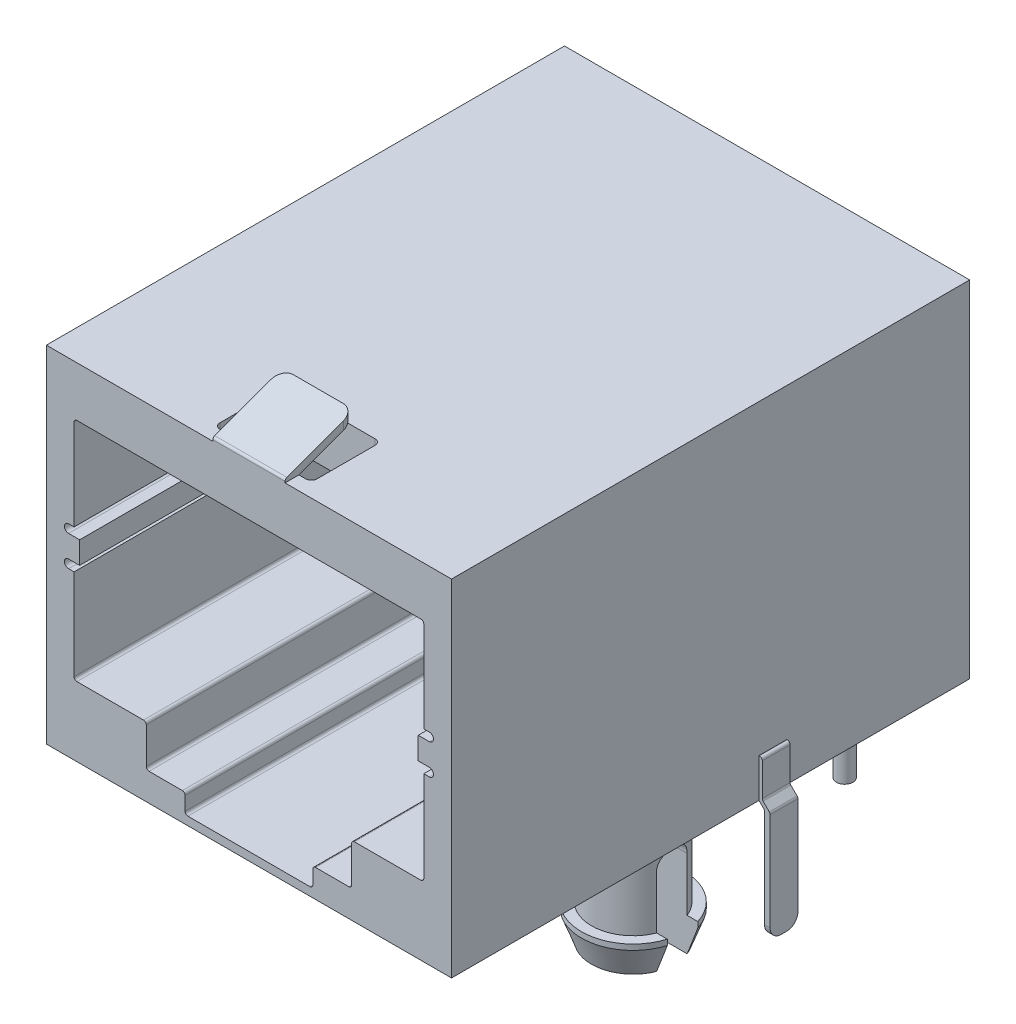
SolidWorks part; units mm, degrees
ref_plane "Plano frontal" through (0, 0, 0) normal (0, 0, 1) x (1, 0, 0)
ref_plane "Plano superior" through (0, 0, 0) normal (0, 1, 0) x (1, 0, 0)
ref_plane "Plano direito" through (0, 0, 0) normal (1, 0, 0) x (0, 0, -1)
sketch "Esboço1" plane through (0, 0, 0) normal (0, 0, 1) x (1, 0, 0)
  line L0 (0, 36.8425) -> (0, 0) construction
  line L2 (-7.3, 12.95) -> (7.3, 12.95)
  line L3 (-7.3, 12.95) -> (-7.3, 0.5)
  line L4 (-7.3, 0.5) -> (7.3, 0.5)
  line L5 (7.3, 12.95) -> (7.3, 0.5)
  line L6 (-7.3, 12.95) -> (7.3, 0.5) construction
  line L7 (-7.3, 0.5) -> (7.3, 12.95) construction
  point P3 (0, 6.725)
  dimension "D1" = 0.5
  dimension "D2" = 12.45
  dimension "D3" = 14.6
extrude "Ressalto-extrusão1" add sketch "Esboço1" along normal blind 9.335 and the other way blind 9.335
sketch "Esboço2" plane through (0, 0, 9.335) normal (0, 0, 1) x (1, 0, 0)
  line L0 (0, 12.95) -> (0, 0.5) construction
  line L1 (7.3, 12.95) -> (-7.3, 12.95) construction
  line L2 (-7.3, 0.5) -> (7.3, 0.5) construction
  line L3 (6.2, 11.15) -> (-6.2, 11.15)
  line L4 (-6.3, 11.15) -> (-6.3, 3) construction
  line L5 (-6.3, 7.075) -> (-2.7204, 7.075) construction
  line L6 (-6.3, 11.05) -> (-6.3, 7.775)
  line L7 (-6.3, 7.775) -> (-6.5, 7.775)
  line L8 (-6.5, 7.775) -> (-6.5, 7.475) construction
  line L9 (-6.2, 3) -> (-3.8, 3)
  line L10 (-3.7, 2.9) -> (-3.7, 1.6)
  line L11 (-3.6, 1.5) -> (-2.4, 1.5)
  line L12 (-2.3, 1.4) -> (-2.3, 0.9)
  line L13 (-2.2, 0.8) -> (2.2, 0.8)
  line L14 (-6.5, 7.475) -> (-6.1, 7.475)
  line L15 (-6.1, 7.475) -> (-6.1, 6.675)
  line L16 (-7.3, 12.95) -> (-7.3, 0.5) construction
  line L17 (-6.3, 3.1) -> (-6.3, 6.375)
  line L18 (-6.5, 6.675) -> (-6.1, 6.675)
  line L19 (-6.3, 6.375) -> (-6.5, 6.375)
  line L20 (6.5, 7.775) -> (6.5, 7.475) construction
  line L21 (6.3, 7.075) -> (2.7204, 7.075) construction
  line L22 (6.3, 11.15) -> (6.3, 3) construction
  line L23 (6.3, 6.375) -> (6.5, 6.375)
  line L24 (6.5, 6.675) -> (6.1, 6.675)
  line L25 (6.3, 3.1) -> (6.3, 6.375)
  line L26 (6.1, 7.475) -> (6.1, 6.675)
  line L27 (6.5, 7.475) -> (6.1, 7.475)
  line L28 (2.3, 1.4) -> (2.3, 0.9)
  line L29 (3.6, 1.5) -> (2.4, 1.5)
  line L30 (3.7, 2.9) -> (3.7, 1.6)
  line L31 (6.2, 3) -> (3.8, 3)
  line L32 (6.3, 7.775) -> (6.5, 7.775)
  line L33 (6.3, 11.05) -> (6.3, 7.775)
  arc A0 (-6.5, 7.775) -> (-6.5, 7.475) centre (-6.5, 7.625) ccw
  arc A1 (-6.5, 6.375) -> (-6.5, 6.675) centre (-6.5, 6.525) cw
  arc A2 (-2.3, 0.9) -> (-2.2, 0.8) centre (-2.2, 0.9) ccw
  arc A3 (-2.4, 1.5) -> (-2.3, 1.4) centre (-2.4, 1.4) cw
  arc A4 (-3.7, 1.6) -> (-3.6, 1.5) centre (-3.6, 1.6) ccw
  arc A5 (-3.8, 3) -> (-3.7, 2.9) centre (-3.8, 2.9) cw
  arc A6 (-6.3, 3.1) -> (-6.2, 3) centre (-6.2, 3.1) ccw
  arc A7 (-6.2, 11.15) -> (-6.3, 11.05) centre (-6.2, 11.05) ccw
  arc A8 (6.2, 11.15) -> (6.3, 11.05) centre (6.2, 11.05) cw
  arc A9 (6.3, 3.1) -> (6.2, 3) centre (6.2, 3.1) cw
  arc A10 (3.8, 3) -> (3.7, 2.9) centre (3.8, 2.9) ccw
  arc A11 (3.7, 1.6) -> (3.6, 1.5) centre (3.6, 1.6) cw
  arc A12 (2.4, 1.5) -> (2.3, 1.4) centre (2.4, 1.4) ccw
  arc A13 (2.3, 0.9) -> (2.2, 0.8) centre (2.2, 0.9) cw
  arc A14 (6.5, 6.375) -> (6.5, 6.675) centre (6.5, 6.525) ccw
  arc A15 (6.5, 7.775) -> (6.5, 7.475) centre (6.5, 7.625) cw
  point P6 (3.7, 1.5)
  point P25 (-6.5, 6.525)
  point P30 (-6.1, 7.075)
  point P34 (-2.3, 1.5)
  point P37 (-3.7, 1.5)
  point P77 (0, 0.8)
  point P78 (0, 11.15)
  point P79 (2.3, 1.5)
  point P80 (6.1, 7.075)
  dimension "D11" = 0.1
  dimension "D1" = 0.3
  dimension "D2" = 0.4
  dimension "D3" = 1.8
  dimension "D4" = 1
  dimension "D5" = 0.2
  dimension "D6" = 0.2
  dimension "D7" = 2.5
  dimension "D8" = 2.6
  dimension "D9" = 1.4
  dimension "D10" = 1
  dimension "D12" = 0.3
extrude "Corte-extrusão1" cut sketch "Esboço2" against normal blind 13
sketch "Esboço3" plane through (0, 0.5, 0) normal (0, -1, 0) x (1, 0, 0)
  line L0 (0, 9.335) -> (0, -9.335) construction
  line L1 (-7.3, 9.335) -> (7.3, 9.335) construction
  line L2 (-7.3, -9.335) -> (7.3, -9.335) construction
  circle A0 centre (-5.715, 1.205) radius 1.5
  circle A1 centre (-4.445, -5.145) radius 0.3
  circle A2 centre (-3.175, -7.685) radius 0.3
  circle A3 centre (5.715, 1.205) radius 1.5
  circle A4 centre (-1.905, -5.145) radius 0.3
  circle A5 centre (-0.635, -7.685) radius 0.3
  circle A6 centre (0.635, -5.145) radius 0.3
  circle A7 centre (1.905, -7.685) radius 0.3
  circle A8 centre (3.175, -5.145) radius 0.3
  circle A9 centre (4.445, -7.685) radius 0.3
  dimension "D1" = 0.6
  dimension "D2" = 0.6
  dimension "D9" = 3
  dimension "D3" = 1.27
  dimension "D4" = 1.27
  dimension "D5" = 5.715
  dimension "D6" = 8.13
  dimension "D7" = 6.35
  dimension "D8" = 2.54
  dimension "D10" = 4
extrude "Ressalto-extrusão2" add sketch "Esboço3" along normal blind 3.68
sketch "Esboço4" plane through (0, -3.18, 0) normal (0, -1, 0) x (1, 0, 0)
  circle A0 centre (-5.715, 1.205) radius 1.5 construction
  circle A1 centre (5.715, 1.205) radius 1.5 construction
  circle A2 centre (-5.715, 1.205) radius 1.5
  circle A3 centre (5.715, 1.205) radius 1.5
extrude "Ressalto-extrusão3" add sketch "Esboço4" against normal blind 1 draft 20 draft outward yes
sketch "Esboço5" plane through (0, -2.18, 0) normal (0, 1, 0) x (1, 0, 0)
  circle A0 centre (-5.715, -1.205) radius 1.864 construction
  circle A1 centre (5.715, -1.205) radius 1.864 construction
  circle A2 centre (-5.715, -1.205) radius 1.864
  circle A3 centre (5.715, -1.205) radius 1.864
extrude "Ressalto-extrusão4" add sketch "Esboço5" along normal blind 0.2
sketch "Esboço7" plane through (0, 0.5, 0) normal (0, -1, 0) x (1, 0, 0)
  line L0 (0, 9.335) -> (0, -9.335) construction
  line L1 (-7.3, 9.335) -> (7.3, 9.335) construction
  line L2 (-7.3, -9.335) -> (7.3, -9.335) construction
  line L3 (-3.175, -7.985) -> (-3.175, 9.335) construction
  line L4 (-3.175, -7.985) -> (-3.175, -9.335) construction
  line L5 (-3.825, 7.1522) -> (-2.525, 7.1522)
  line L6 (-3.825, 7.1522) -> (-3.825, 2.6522)
  line L7 (-3.825, 2.6522) -> (-2.525, 2.6522)
  line L8 (-2.525, 7.1522) -> (-2.525, 2.6522)
  line L9 (-3.825, 7.1522) -> (-2.525, 2.6522) construction
  line L10 (-3.825, 2.6522) -> (-2.525, 7.1522) construction
  line L11 (-3.825, -8.2792) -> (-2.525, -8.2792)
  line L12 (-3.825, -8.2792) -> (-3.825, -9.1461)
  line L13 (-3.825, -9.1461) -> (-2.525, -9.1461)
  line L14 (-2.525, -8.2792) -> (-2.525, -9.1461)
  line L15 (-3.825, -8.2792) -> (-2.525, -9.1461) construction
  line L16 (-3.825, -9.1461) -> (-2.525, -8.2792) construction
  line L17 (3.825, -9.1461) -> (2.525, -8.2792) construction
  line L18 (3.825, -8.2792) -> (2.525, -9.1461) construction
  line L19 (3.825, 2.6522) -> (2.525, 7.1522) construction
  line L20 (3.825, 7.1522) -> (2.525, 2.6522) construction
  line L21 (3.175, -7.985) -> (3.175, -9.335) construction
  line L22 (3.175, -7.985) -> (3.175, 9.335) construction
  line L23 (2.525, -8.2792) -> (2.525, -9.1461)
  line L24 (3.825, -9.1461) -> (2.525, -9.1461)
  line L25 (3.825, -8.2792) -> (3.825, -9.1461)
  line L26 (3.825, -8.2792) -> (2.525, -8.2792)
  line L27 (2.525, 7.1522) -> (2.525, 2.6522)
  line L28 (3.825, 2.6522) -> (2.525, 2.6522)
  line L29 (3.825, 7.1522) -> (3.825, 2.6522)
  line L30 (3.825, 7.1522) -> (2.525, 7.1522)
  circle A0 centre (-3.175, -7.685) radius 0.3 construction
  circle A1 centre (-3.175, -7.685) radius 0.3 construction
  point P12 (-3.175, 4.9022)
  point P18 (-3.175, -8.7126)
  point P35 (3.175, -8.7126)
  point P36 (3.175, 4.9022)
  dimension "D1" = 2.1828
  dimension "D2" = 1.3
  dimension "D3" = 4.5
  dimension "D4" = 1.3
extrude "Ressalto-extrusão5" add sketch "Esboço7" along normal blind 0.5
sketch "Esboço8" plane through (7.3, 0, 0) normal (1, 0, 0) x (0, 0, -1)
  line L0 (-1.205, -3.18) -> (-1.205, 4.3732) construction
  line L1 (-2.705, -3.18) -> (0.295, -3.18) construction
  line L2 (-1.755, -0.05) -> (-1.755, -3.18)
  line L3 (-0.655, -0.05) -> (-0.655, -3.18)
  line L4 (9.335, 0.5) -> (-9.335, 0.5) construction
  line L5 (-1.755, -3.18) -> (-0.655, -3.18)
  arc A0 (-0.655, -0.05) -> (-1.755, -0.05) centre (-1.205, -0.05) ccw
  dimension "D1" = 1.1
extrude "Corte-extrusão2" cut sketch "Esboço8" against normal through all and the other way through all
ref_plane "Plano2" through (0, 0, -2.245) normal (0, 0, 1) x (1, 0, 0)
sketch "Esboço9" plane through (0, 0, -2.245) normal (0, 0, 1) x (1, 0, 0)
  line L0 (-7.3, 1.9) -> (-7.32, 1.9)
  line L1 (-7.3, 12.95) -> (-7.3, 0.5) construction
  line L2 (-7.42, 1.8) -> (-7.42, 0.6214)
  line L3 (-7.4493, 0.5507) -> (-7.6707, 0.3293)
  line L4 (-7.7, 0.2586) -> (-7.7, -3.68)
  line L5 (-7.7, -3.68) -> (-7.5, -3.68)
  line L6 (-7.5, -3.68) -> (-7.5, 0.2586)
  line L7 (-7.4707, 0.3293) -> (-7.3, 0.5)
  line L8 (-7.6, -3.68) -> (-7.6, -2.2361) construction
  line L9 (-7.3, 1.9) -> (-7.3, 0.5)
  line L10 (-7.215, 0.5) -> (-4.215, 0.5) construction
  line L11 (-7.1105, -3.18) -> (-4.3195, -3.18) construction
  line L12 (0, 4.2672) -> (0, -7.912) construction
  line L13 (7.6, -3.68) -> (7.6, -2.2361) construction
  line L14 (7.3, 1.9) -> (7.3, 0.5)
  line L15 (7.4707, 0.3293) -> (7.3, 0.5)
  line L16 (7.5, -3.68) -> (7.5, 0.2586)
  line L17 (7.7, -3.68) -> (7.5, -3.68)
  line L18 (7.7, 0.2586) -> (7.7, -3.68)
  line L19 (7.4493, 0.5507) -> (7.6707, 0.3293)
  line L20 (7.42, 1.8) -> (7.42, 0.6214)
  line L21 (7.3, 1.9) -> (7.32, 1.9)
  arc A0 (-7.5, 0.2586) -> (-7.4707, 0.3293) centre (-7.4, 0.2586) cw
  arc A1 (-7.6707, 0.3293) -> (-7.7, 0.2586) centre (-7.6, 0.2586) ccw
  arc A2 (-7.42, 0.6214) -> (-7.4493, 0.5507) centre (-7.52, 0.6214) cw
  arc A3 (-7.32, 1.9) -> (-7.42, 1.8) centre (-7.32, 1.8) ccw
  arc A4 (7.32, 1.9) -> (7.42, 1.8) centre (7.32, 1.8) cw
  arc A5 (7.42, 0.6214) -> (7.4493, 0.5507) centre (7.52, 0.6214) ccw
  arc A6 (7.6707, 0.3293) -> (7.7, 0.2586) centre (7.6, 0.2586) cw
  arc A7 (7.5, 0.2586) -> (7.4707, 0.3293) centre (7.4, 0.2586) ccw
  point P20 (-7.5, 0.3)
  point P23 (-7.7, 0.3)
  point P28 (-7.42, 1.9)
  point P49 (7.42, 1.9)
  point P50 (7.7, 0.3)
  point P51 (7.5, 0.3)
  dimension "D7" = 0.1
  dimension "D1" = 135
  dimension "D2" = 7.6
  dimension "D3" = 0.12
  dimension "D4" = 0.5
  dimension "D5" = 1.4
extrude "Ressalto-extrusão6" add sketch "Esboço9" along normal blind 0.5 and the other way blind 0.5
fillet "Filete1" radius 0.4 4 edges at (-7.6, -3.68, -1.745) (-7.6, -3.68, -2.745) (7.6, -3.68, -2.745) (7.6, -3.68, -1.745)
sketch "Esboço11" plane through (0, 0, -3.665) normal (0, 0, 1) x (1, 0, 0)
  line L0 (0, 12.95) -> (0, 0.5) construction
  line L1 (7.3, 12.95) -> (-7.3, 12.95) construction
  line L2 (-7.3, 0.5) -> (7.3, 0.5) construction
  line L3 (6.2, 11.15) -> (-6.2, 11.15) construction
  line L4 (-0.25, 11.15) -> (-0.75, 11.15)
  line L5 (-0.25, 11.15) -> (-0.25, 7.075)
  line L6 (-0.25, 7.075) -> (-0.75, 7.075)
  line L7 (-0.75, 11.15) -> (-0.75, 7.075)
  line L8 (-0.5, 7.075) -> (-0.5, 11.15) construction
  line L9 (-6.1, 7.075) -> (6.1, 7.075) construction
  line L10 (-6.1, 7.475) -> (-6.1, 6.675) construction
  line L11 (6.1, 6.675) -> (6.1, 7.475) construction
  line L12 (0.75, 11.15) -> (0.25, 11.15)
  line L13 (0.75, 11.15) -> (0.75, 7.075)
  line L14 (0.75, 7.075) -> (0.25, 7.075)
  line L15 (0.25, 11.15) -> (0.25, 7.075)
  line L16 (0.5, 7.075) -> (0.5, 11.15) construction
  line L17 (1.75, 11.15) -> (1.25, 11.15)
  line L18 (1.75, 11.15) -> (1.75, 7.075)
  line L19 (1.75, 7.075) -> (1.25, 7.075)
  line L20 (1.25, 11.15) -> (1.25, 7.075)
  line L21 (1.5, 7.075) -> (1.5, 11.15) construction
  line L22 (2.75, 11.15) -> (2.25, 11.15)
  line L23 (2.75, 11.15) -> (2.75, 7.075)
  line L24 (2.75, 7.075) -> (2.25, 7.075)
  line L25 (2.25, 11.15) -> (2.25, 7.075)
  line L26 (2.5, 7.075) -> (2.5, 11.15) construction
  line L27 (3.75, 11.15) -> (3.25, 11.15)
  line L28 (3.75, 11.15) -> (3.75, 7.075)
  line L29 (3.75, 7.075) -> (3.25, 7.075)
  line L30 (3.25, 11.15) -> (3.25, 7.075)
  line L31 (3.5, 7.075) -> (3.5, 11.15) construction
  line L32 (-1.25, 11.15) -> (-1.75, 11.15)
  line L33 (-1.25, 11.15) -> (-1.25, 7.075)
  line L34 (-1.25, 7.075) -> (-1.75, 7.075)
  line L35 (-1.75, 11.15) -> (-1.75, 7.075)
  line L36 (-1.5, 7.075) -> (-1.5, 11.15) construction
  line L37 (-2.25, 11.15) -> (-2.75, 11.15)
  line L38 (-2.25, 11.15) -> (-2.25, 7.075)
  line L39 (-2.25, 7.075) -> (-2.75, 7.075)
  line L40 (-2.75, 11.15) -> (-2.75, 7.075)
  line L41 (-2.5, 7.075) -> (-2.5, 11.15) construction
  line L42 (-3.25, 11.15) -> (-3.75, 11.15)
  line L43 (-3.25, 11.15) -> (-3.25, 7.075)
  line L44 (-3.25, 7.075) -> (-3.75, 7.075)
  line L45 (-3.75, 11.15) -> (-3.75, 7.075)
  line L46 (-3.5, 7.075) -> (-3.5, 11.15) construction
  dimension "D1" = 0.5
  dimension "D2" = 0.5
  dimension "D3" = 5
  dimension "D4" = 4
extrude "Ressalto-extrusão7" add sketch "Esboço11" along normal blind 3
chamfer "Chanfro1" distance 2 angle 45 8 edges at (3.5, 7.075, -0.665) (2.5, 7.075, -0.665) (1.5, 7.075, -0.665) (0.5, 7.075, -0.665) (-0.5, 7.075, -0.665) (-1.5, 7.075, -0.665) (-2.5, 7.075, -0.665) (-3.5, 7.075, -0.665)
sketch "Esboço12" plane through (0, 12.95, 0) normal (0, 1, 0) x (1, 0, 0)
  line L0 (0, -9.335) -> (0, -1.7772) construction
  line L1 (7.3, -9.335) -> (-7.3, -9.335) construction
  line L3 (-1.55, -6.335) -> (1.55, -6.335)
  line L4 (-1.75, -6.535) -> (-1.75, -8.635)
  line L5 (-1.55, -8.835) -> (1.55, -8.835)
  line L6 (1.75, -6.535) -> (1.75, -8.635)
  line L7 (-1.75, -6.335) -> (1.75, -8.835) construction
  line L8 (-1.75, -8.835) -> (1.75, -6.335) construction
  arc A0 (1.55, -6.335) -> (1.75, -6.535) centre (1.55, -6.535) cw
  arc A1 (1.55, -8.835) -> (1.75, -8.635) centre (1.55, -8.635) ccw
  arc A2 (-1.75, -8.635) -> (-1.55, -8.835) centre (-1.55, -8.635) ccw
  arc A3 (-1.55, -6.335) -> (-1.75, -6.535) centre (-1.55, -6.535) ccw
  point P5 (0, -7.585)
  dimension "D4" = 0.2
  dimension "D1" = 0.5
  dimension "D2" = 2.5
  dimension "D3" = 3.5
extrude "Corte-extrusão3" cut sketch "Esboço12" against normal up to next
sketch "Esboço13" plane through (0, 0, 0) normal (1, 0, 0) x (0, 0, -1)
  line L0 (-9.2692, 13.092) -> (-6.835, 13.9779)
  line L1 (-6.835, 13.9779) -> (-6.835, 13.6779)
  line L2 (-6.835, 13.6779) -> (-8.835, 12.95)
  line L3 (9.335, 12.95) -> (-9.335, 12.95) construction
  line L4 (-9.335, 0.5) -> (-9.335, 12.95) construction
  line L5 (-9.335, 12.95) -> (-9.335, 12.998)
  line L6 (-9.335, 12.95) -> (-8.835, 12.95)
  arc A0 (-9.2692, 13.092) -> (-9.335, 12.998) centre (-9.235, 12.998) ccw
  point P12 (-9.335, 13.068)
  dimension "D5" = 0.1
  dimension "D1" = 0.5
  dimension "D2" = 20
  dimension "D3" = 2.5
  dimension "D4" = 0.3
extrude "Ressalto-extrusão8" add sketch "Esboço13" along normal blind 1.3 and the other way blind 1.3
fillet "Filete2" radius 0.4 2 edges at (-1.3, 13.8279, 6.835) (1.3, 13.8279, 6.835)
